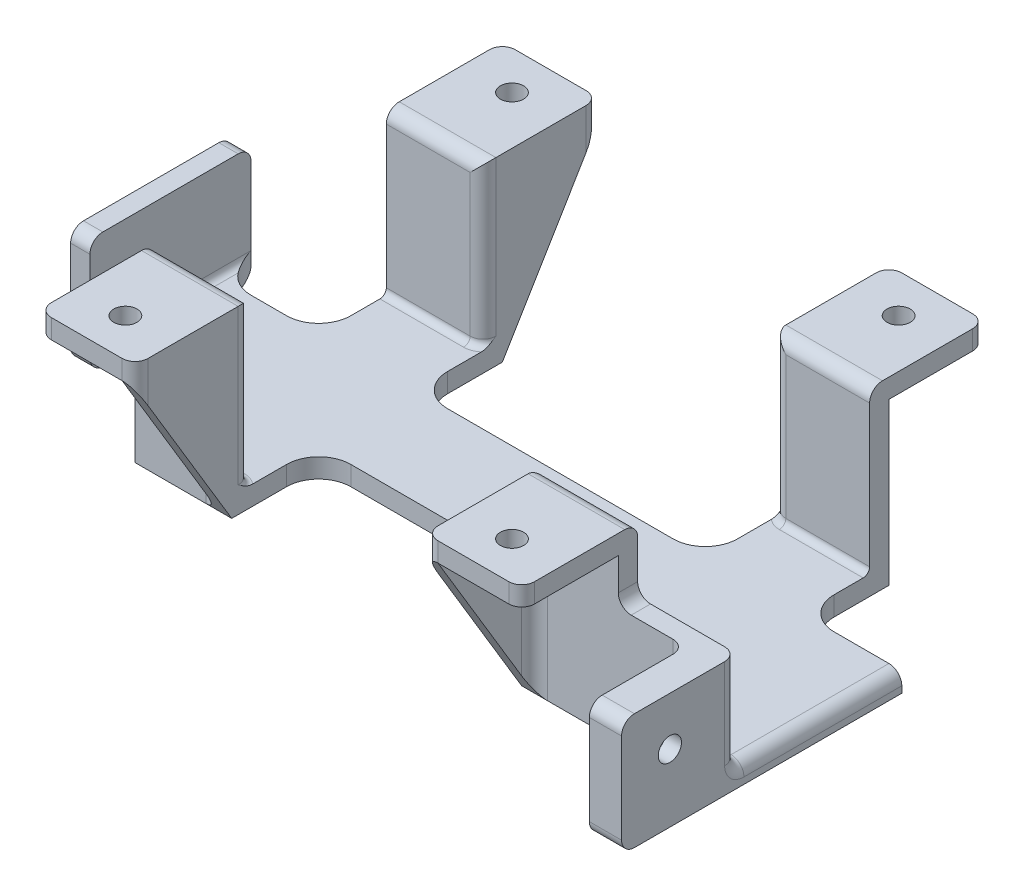
SolidWorks part; units mm, degrees
ref_plane "Front Plane" through (0, 0, 0) normal (0, 0, 1) x (1, 0, 0)
ref_plane "Top Plane" through (0, 0, 0) normal (0, 1, 0) x (1, 0, 0)
ref_plane "Right Plane" through (0, 0, 0) normal (1, 0, 0) x (0, 0, -1)
sketch "Sketch1" plane through (0, 0, 0) normal (0, 1, 0) x (1, 0, 0)
  line L0 (-53, 7.5) -> (-42.5, 7.5)
  line L1 (-37.5, 12.5) -> (-37.5, 21)
  line L2 (-37.5, 21) -> (-22.5, 21)
  line L3 (-22.5, 21) -> (-22.5, 12.5)
  line L4 (-17.5, 7.5) -> (17.5, 7.5)
  line L5 (22.5, 12.5) -> (22.5, 21)
  line L6 (22.5, 21) -> (37.5, 21)
  line L7 (37.5, 21) -> (37.5, 12.5)
  line L8 (42.5, 7.5) -> (53, 7.5)
  line L9 (-53, 7.5) -> (-53, -7.5)
  line L10 (53, 7.5) -> (53, -7.5)
  line L11 (-53, 0) -> (53, 0) construction
  line L12 (42.5, -7.5) -> (53, -7.5)
  line L13 (37.5, -21) -> (37.5, -12.5)
  line L14 (22.5, -21) -> (37.5, -21)
  line L15 (22.5, -12.5) -> (22.5, -21)
  line L16 (-17.5, -7.5) -> (17.5, -7.5)
  line L17 (-22.5, -21) -> (-22.5, -12.5)
  line L18 (-37.5, -21) -> (-22.5, -21)
  line L19 (-37.5, -12.5) -> (-37.5, -21)
  line L20 (-53, -7.5) -> (-42.5, -7.5)
  arc A0 (37.5, 12.5) -> (42.5, 7.5) centre (42.5, 12.5) ccw
  arc A1 (17.5, 7.5) -> (22.5, 12.5) centre (17.5, 12.5) ccw
  arc A2 (-22.5, 12.5) -> (-17.5, 7.5) centre (-17.5, 12.5) ccw
  arc A3 (-42.5, 7.5) -> (-37.5, 12.5) centre (-42.5, 12.5) ccw
  arc A4 (37.5, -12.5) -> (42.5, -7.5) centre (42.5, -12.5) cw
  arc A5 (17.5, -7.5) -> (22.5, -12.5) centre (17.5, -12.5) cw
  arc A6 (-22.5, -12.5) -> (-17.5, -7.5) centre (-17.5, -12.5) cw
  arc A7 (-42.5, -7.5) -> (-37.5, -12.5) centre (-42.5, -12.5) cw
  point P2 (0, 0)
  point P13 (0, 7.5)
  point P15 (30, 21)
  point P16 (-38.2339, 7.5)
  point P19 (37.5, 7.5)
  point P20 (-30, 21)
  point P23 (22.5, 7.5)
  point P26 (-22.5, 7.5)
  point P29 (-37.5, 7.5)
  dimension "D6" = 5
  dimension "D1" = 21
  dimension "D2" = 7.5
  dimension "D3" = 106
  dimension "D4" = 60
  dimension "D5" = 15
extrude "Boss-Extrude1" add sketch "Sketch1" along normal blind 3
sketch "Sketch2" plane through (0, 3, 0) normal (0, 1, 0) x (1, 0, 0)
  line L0 (-22.5, 12.5) -> (-22.5, 21) construction
  line L1 (-37.5, 21) -> (-22.5, 21)
  line L2 (-37.5, 21) -> (-37.5, 18)
  line L3 (-37.5, 18) -> (-22.5, 18)
  line L4 (-22.5, 21) -> (-22.5, 18)
  line L5 (37.5, 12.5) -> (37.5, 21) construction
  line L6 (22.5, 21) -> (37.5, 21)
  line L7 (22.5, 21) -> (22.5, 18)
  line L8 (22.5, 18) -> (37.5, 18)
  line L9 (37.5, 21) -> (37.5, 18)
  line L10 (-22.5, -21) -> (-22.5, -12.5) construction
  line L11 (-37.5, -21) -> (-22.5, -21)
  line L12 (-37.5, -21) -> (-37.5, -18)
  line L13 (-37.5, -18) -> (-22.5, -18)
  line L14 (-22.5, -21) -> (-22.5, -18)
  line L15 (37.5, -21) -> (37.5, -12.5) construction
  line L16 (22.5, -21) -> (37.5, -21)
  line L17 (22.5, -21) -> (22.5, -18)
  line L18 (22.5, -18) -> (37.5, -18)
  line L19 (37.5, -21) -> (37.5, -18)
  dimension "D1" = 3
extrude "Boss-Extrude2" add sketch "Sketch2" along normal blind 25
sketch "Sketch3" plane through (0, 0, 0) normal (0, -1, 0) x (1, 0, 0)
  line L0 (-53, -7.5) -> (-53, 7.5) construction
  line L1 (-53, 12.5) -> (-56, 12.5)
  line L2 (-53, 12.5) -> (-53, -12.5)
  line L3 (-53, -12.5) -> (-56, -12.5)
  line L4 (-56, 12.5) -> (-56, -12.5)
  point P4 (0, 0)
  point P5 (-53, 0)
  point P6 (-53, 0)
  dimension "D1" = 3
  dimension "D2" = 25
extrude "Boss-Extrude3" add sketch "Sketch3" against normal blind 18
fillet "Fillet1" radius 5 2 edges at (-53, 1.5, -7.5) (-53, 1.5, 7.5)
sketch "Sketch4" plane through (0, 0, 21) normal (0, 0, 1) x (1, 0, 0)
  line L0 (-22.5, 28) -> (-22.5, 0) construction
  line L1 (-37.5, 28) -> (-22.5, 28)
  line L2 (-37.5, 28) -> (-37.5, 25)
  line L3 (-37.5, 25) -> (-22.5, 25)
  line L4 (-22.5, 28) -> (-22.5, 25)
  dimension "D1" = 3
extrude "Boss-Extrude4" add sketch "Sketch4" along normal blind 15
sketch "Sketch5" plane through (0, 28, 0) normal (0, 1, 0) x (1, 0, 0)
  line L0 (-53, 0) -> (53, 0) construction
  line L1 (-53, 12.5) -> (-53, -12.5) construction
  line L2 (53, -7.5) -> (53, 7.5) construction
  circle A0 centre (-30, -30) radius 1.8
  dimension "D3" = 3.6
  dimension "D1" = 30
  dimension "D2" = 30
extrude "Cut-Extrude1" cut sketch "Sketch5" against normal blind 20
sketch "Sketch6" plane through (-22.5, 0, 0) normal (1, 0, 0) x (0, 0, -1)
  line L0 (-36, 25) -> (-21, 25)
  line L1 (-21, 25) -> (-21, 0)
  line L2 (-21, 0) -> (-36, 25)
extrude "Boss-Extrude5" add sketch "Sketch6" against normal blind 2
mirror "Mirror1" about plane through (0, 0, 0) normal (0, 0, 1) of "Boss-Extrude5", "Cut-Extrude1", "Boss-Extrude4"
mirror "Mirror2" about plane through (0, 0, 0) normal (1, 0, 0) of "Mirror1", "Boss-Extrude5", "Cut-Extrude1", "Boss-Extrude4"
sketch "Sketch7" plane through (0, 0, 0) normal (0, -1, 0) x (1, 0, 0)
  line L1 (37.5, 21) -> (53, 21)
  line L2 (37.5, 21) -> (37.5, 7.5)
  line L3 (37.5, 7.5) -> (53, 7.5)
  line L4 (53, 21) -> (53, 7.5)
  dimension "D1" = 13.5
  dimension "D2" = 15.5
extrude "Boss-Extrude6" add sketch "Sketch7" against normal blind 3
sketch "Sketch8" plane through (0, 0, 21) normal (0, 0, 1) x (1, 0, 0)
  line L0 (37.5, 25) -> (37.5, 3) construction
  line L1 (53, 3) -> (37.5, 3)
  line L2 (53, 3) -> (53, 18)
  line L3 (53, 18) -> (37.5, 18)
  line L4 (37.5, 3) -> (37.5, 18)
  dimension "D1" = 15
extrude "Boss-Extrude7" add sketch "Sketch8" against normal blind 3
sketch "Sketch9" plane through (0, 0, 21) normal (0, 0, 1) x (1, 0, 0)
  line L0 (24.5, 0) -> (53, 0) construction
  line L1 (53, 18) -> (48, 18)
  line L2 (53, 18) -> (53, 0)
  line L3 (53, 0) -> (48, 0)
  line L4 (48, 18) -> (48, 0)
  dimension "D1" = 5
extrude "Boss-Extrude8" add sketch "Sketch9" along normal blind 15
sketch "Sketch10" plane through (53, 0, 0) normal (1, 0, 0) x (0, 0, -1)
  line L0 (-36, 0) -> (-36, 18) construction
  line L1 (-18, 18) -> (-36, 18) construction
  circle A0 centre (-28.5, 10.5) radius 1.8
  dimension "D1" = 3.6
  dimension "D2" = 7.5
  dimension "D3" = 7.5
extrude "Cut-Extrude2" cut sketch "Sketch10" against normal blind 15
sketch "Sketch11" plane through (48, 0, 0) normal (-1, 0, 0) x (0, 0, 1)
  line L0 (36, 18) -> (21, 18) construction
  line L1 (30.1599, 13.375) -> (26.8401, 13.375)
  line L2 (26.8401, 13.375) -> (25.1802, 10.5)
  line L3 (25.1802, 10.5) -> (26.8401, 7.625)
  line L4 (26.8401, 7.625) -> (30.1599, 7.625)
  line L5 (30.1599, 7.625) -> (31.8198, 10.5)
  line L6 (31.8198, 10.5) -> (30.1599, 13.375)
  circle A0 centre (28.5, 10.5) radius 2.875 construction
  dimension "D1" = 5.75
extrude "Cut-Extrude3" cut sketch "Sketch11" against normal blind 2.5
fillet "Fillet2" radius 2 20 edges at (-22.5, 26.5, 36) (22.5, 26.5, 36) (37.5, 26.5, 36) (-37.5, 26.5, -36) (-22.5, 26.5, -36) (22.5, 26.5, -36) (37.5, 26.5, -36) (-22.5, 15.5, -18) (-22.5, 15.5, 18) (22.5, 15.5, -18) (22.5, 15.5, 18) (30, 28, -18) (30, 28, 18) (-30, 28, -18) (-30, 28, 18) (-54.5, 0, -12.5) (-54.5, 0, 12.5) (-54.5, 18, -12.5) (-54.5, 18, 12.5) (-37.5, 26.5, 36)
fillet "Fillet3" radius 1 9 edges at (23.0858, 3, 18.5858) (38.75, 3, 18) (-23.0858, 3, 18.5858) (-31, 3, 18) (23.0858, 3, -18.5858) (31, 3, -18) (-23.0858, 3, -18.5858) (-31, 3, -18) (-53, 3, 0)
fillet "Fillet4" radius 2 8 edges at (53, 3, 4.75) (53, 3.2929, 17.7071) (53, 11, 18) (48, 9, 21) (-24.5, 12.5, 21) (24.5, 12.5, 21) (-24.5, 12.5, -21) (24.5, 12.5, -21)
fillet "Fillet5" radius 2 3 edges at (50.5, 0, 36) (37.5, 18, 19.5) (50.5, 18, 36)
